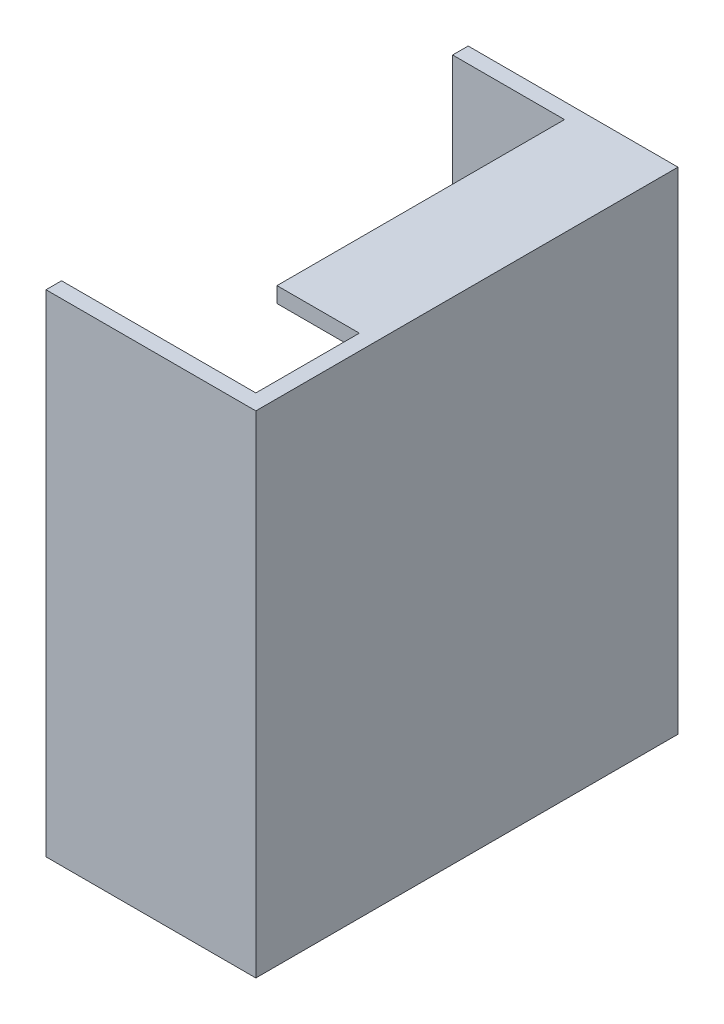
SolidWorks part; units mm, degrees
ref_plane "Front Plane" through (0, 0, 0) normal (0, 0, 1) x (1, 0, 0)
ref_plane "Top Plane" through (0, 0, 0) normal (0, 1, 0) x (1, 0, 0)
ref_plane "Right Plane" through (0, 0, 0) normal (1, 0, 0) x (0, 0, -1)
sketch "Sketch1" plane through (0, 0, 0) normal (1, 0, 0) x (0, 0, -1)
  line L1 (-14.986, 38.735) -> (32.004, 38.735)
  line L3 (-31.9039, -38.989) -> (32.004, -38.989)
  line L4 (32.004, 38.735) -> (32.004, -38.989)
  line L5 (-34.4439, 32.385) -> (-14.986, 32.385) construction
  line L6 (-31.9039, 38.735) -> (-31.9039, -38.989)
  line L8 (-34.4439, 32.385) -> (-34.4439, -41.529)
  line L9 (-34.4439, -41.529) -> (34.544, -41.529)
  line L10 (34.544, 38.735) -> (34.544, -41.529)
  line L12 (-14.986, 38.735) -> (32.004, 38.735)
  line L13 (-14.986, 32.385) -> (-14.986, 38.735) construction
  line L16 (-34.4439, 32.385) -> (-34.4439, 38.735)
  line L18 (-14.986, 38.735) -> (-31.9039, 38.735)
  line L20 (-34.4439, 38.735) -> (-31.9039, 38.735)
  line L21 (32.004, 38.735) -> (34.544, 38.735)
  line L22 (-14.986, 38.735) -> (-14.986, 36.195)
  line L23 (-14.986, 36.195) -> (32.004, 36.195)
  line L24 (32.004, 38.735) -> (32.004, 36.195)
  point P0 (0, 0)
  point P6 (0, 0)
  dimension "D1" = 77.724
  dimension "D2" = 63.9079
  dimension "D3" = 6.35
  dimension "D4" = 46.99
  dimension "D5" = 2.54
  dimension "D6" = 2.54
  dimension "D7" = 2.54
  dimension "D8" = 2.54
extrude "Boss-Extrude3" add sketch "Sketch1" along normal blind 2.54 contours L4 L1 L3 | L8 L9 L10 L1 L4 L3 | L22 L23 L4 L1 region at (0, -1.0525, 0.1582) region at (0, 37.465, -8.509) region at (0, 37.6766, -33.274)
extrude "Boss-Extrude4" add sketch "Sketch1<5>" against normal blind 31.75 contours L21 L4 L3 L20 L16 L8 L9 L10 region at (0, 37.6766, -33.274)
sketch "Sketch1<5>" plane through (0, 0, 0) normal (1, 0, 0) x (0, 0, -1) same geometry as "Sketch1"
extrude "Boss-Extrude5" add sketch "Sketch1<6>" against normal blind 13.462 contours L22 L23 L4 L1 region at (0, 37.465, -8.509)
sketch "Sketch1<6>" plane through (0, 0, 0) normal (1, 0, 0) x (0, 0, -1) same geometry as "Sketch1"
sketch "Sketch2" plane through (0, 0, 0) normal (-1, 0, 0) x (0, 0, 1)
  line L0 (14.986, 37.465) -> (14.986, -38.989) construction
  line L1 (14.986, 38.735) -> (14.986, 36.195) construction
  line L2 (31.9039, -38.989) -> (-32.004, -38.989) construction
  line L3 (14.986, -38.989) -> (31.9039, -38.989) construction
  line L4 (31.9039, -38.989) -> (31.9039, 37.465) construction
  line L5 (31.9039, 38.735) -> (31.9039, -38.989) construction
  line L6 (31.9039, 37.465) -> (14.986, 37.465) construction
  line L7 (16.256, -0.889) -> (16.256, -38.989) construction
  line L8 (14.986, -38.989) -> (31.9039, -38.989) construction
  line L9 (14.986, -0.889) -> (31.9039, -0.889) construction
  line L10 (23.445, -0.889) -> (31.9039, -0.889) construction
  line L19 (20.066, -0.889) -> (20.066, -38.989) construction
  line L26 (16.256, -0.889) -> (18.796, -0.889)
  line L27 (16.256, -0.889) -> (16.256, -32.639)
  line L29 (18.796, -0.889) -> (18.796, -32.639)
  line L30 (16.256, -32.639) -> (18.796, -32.639)
  dimension "D1" = 0
  dimension "D2" = 38.1
  dimension "D3" = 1.27
  dimension "D4" = 3.81
  dimension "D5" = 2.54
  dimension "D6" = 6.35
extrude "Boss-Extrude6" add sketch "Sketch2" along normal blind 34.29
sketch "Sketch3" plane through (0, -32.639, 0) normal (0, -1, 0) x (1, 0, 0)
  line L0 (-34.29, 18.796) -> (-40.0863, 18.796)
  line L1 (-40.4275, 17.6254) -> (-34.29, 13.716)
  line L3 (-34.29, 18.796) -> (-34.29, 13.716)
  arc A0 (-40.0863, 18.796) -> (-40.4275, 17.6254) centre (-40.0863, 18.161) ccw
  dimension "D1" = 0.635
  dimension "D2" = 5.08
extrude "Boss-Extrude7" add sketch "Sketch3" against normal up to surface (31.75 mm away) up to face at (-17.145, -0.889, 17.526)
